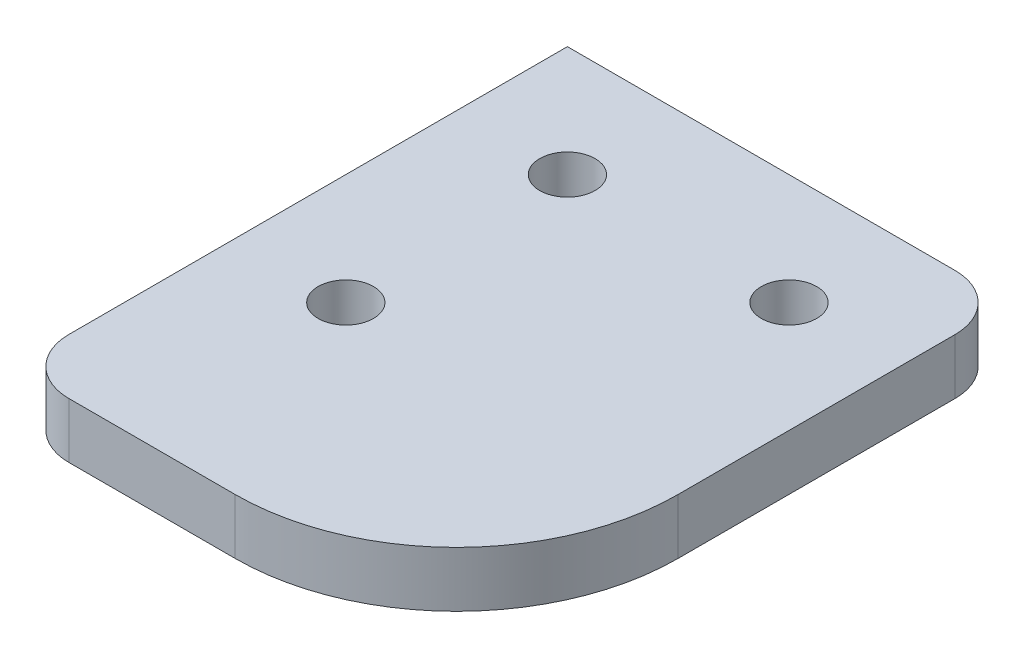
SolidWorks part; units mm, degrees
ref_plane "Front" through (0, 0, 0) normal (0, 0, 1) x (1, 0, 0)
ref_plane "Top" through (0, 0, 0) normal (0, 1, 0) x (1, 0, 0)
ref_plane "Right" through (0, 0, 0) normal (1, 0, 0) x (0, 0, -1)
sketch "Sketch1" plane through (0, 0, 0) normal (0, 1, 0) x (1, 0, 0)
  line L0 (0, 14.2138) -> (0, -4.1016) construction
  line L1 (-20, 20) -> (20, 20)
  line L2 (-20, 20) -> (-20, -30)
  line L4 (20, 20) -> (20, -10)
  line L5 (-20, -30) -> (0, -30)
  line L6 (-17.0016, 0) -> (16.742, 0) construction
  circle A0 centre (-10, 10) radius 2.5
  circle A3 centre (10, 10) radius 2.5
  arc A4 (20, -10) -> (0, -30) centre (0, -10) cw
  circle A5 centre (-10, -10) radius 2.5
  point P0 (0, 0)
  dimension "D2" = 10
  dimension "D1" = 40
  dimension "D3" = 50
  dimension "D4" = 30
extrude "Boss-Extrude1" add sketch "Sketch1" along normal blind 5
fillet "Fillet1" radius 5 2 edges at (20, 2.5, -20) (-20, 2.5, 30)
